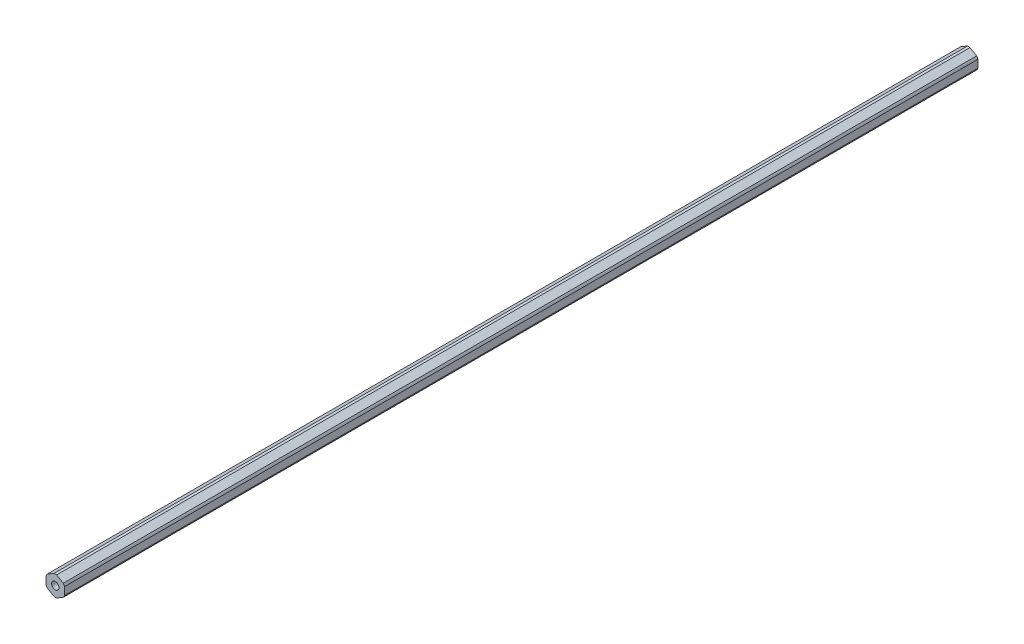
SolidWorks part; units mm, degrees
material "7075-T6, Plate (SS)"
ref_plane "Front Plane" through (0, 0, 0) normal (0, 0, 1) x (1, 0, 0)
ref_plane "Top Plane" through (0, 0, 0) normal (0, 1, 0) x (1, 0, 0)
ref_plane "Right Plane" through (0, 0, 0) normal (1, 0, 0) x (0, 0, -1)
sketch "Sketch1" plane through (0, 0, 0) normal (0, 0, 1) x (1, 0, 0)
  line L1 (-0.893, 6.8168) -> (-5.457, 4.1818)
  line L2 (-6.35, 2.635) -> (-6.35, -2.635)
  line L3 (-5.457, -4.1818) -> (-0.893, -6.8168)
  line L4 (0.893, -6.8168) -> (5.457, -4.1818)
  line L5 (6.35, -2.635) -> (6.35, 2.635)
  line L6 (5.457, 4.1818) -> (0.893, 6.8168)
  arc A0 (-5.457, 4.1818) -> (-6.35, 2.635) centre (0, 0) ccw
  circle A1 centre (0, 0) radius 6.35 construction
  arc A2 (0.893, 6.8168) -> (-0.893, 6.8168) centre (0, 0) ccw
  arc A3 (-6.35, -2.635) -> (-5.457, -4.1818) centre (0, 0) ccw
  arc A4 (-0.893, -6.8168) -> (0.893, -6.8168) centre (0, 0) ccw
  arc A5 (5.457, -4.1818) -> (6.35, -2.635) centre (0, 0) ccw
  arc A6 (6.35, 2.635) -> (5.457, 4.1818) centre (0, 0) ccw
  circle A7 centre (0, 0) radius 2.4892
  dimension "D1" = 12.7
  dimension "D2" = 13.75
  dimension "D3" = 4.9784
extrude "Boss-Extrude1" add sketch "Sketch1" against normal blind 624.84
equation "\"D2@Sketch1\"=13.75mm"
